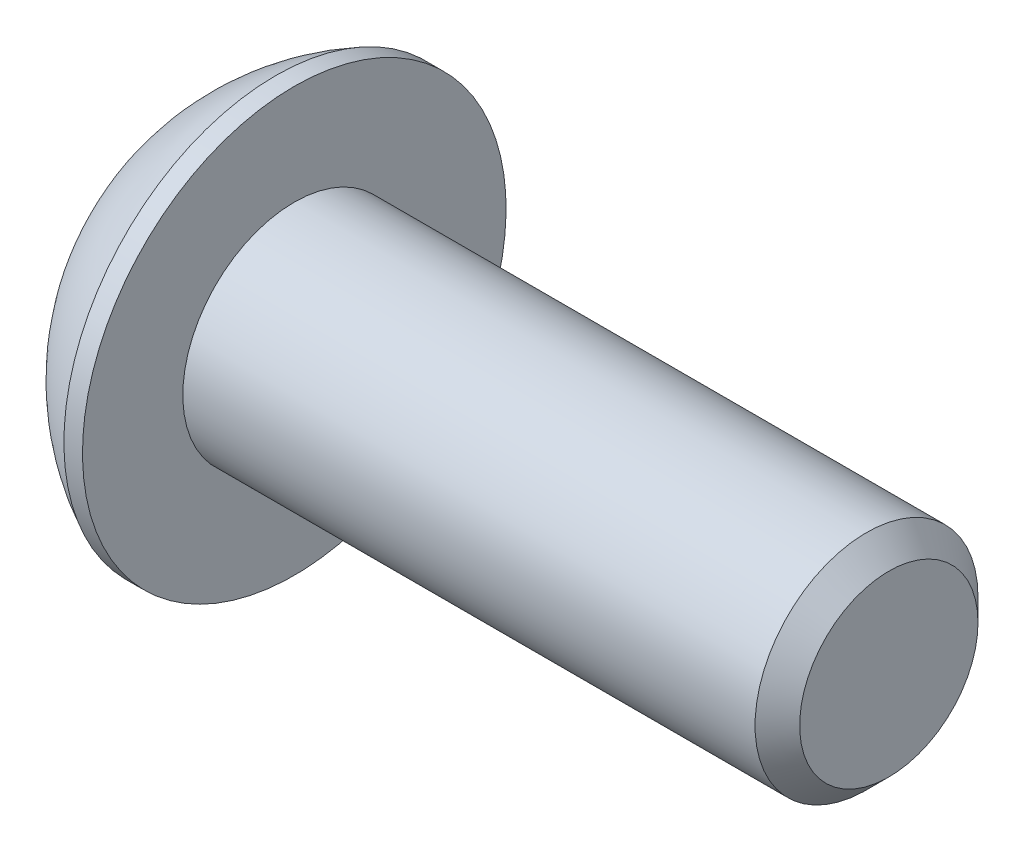
SolidWorks part; units mm, degrees
material "Plain Carbon Steel"
ref_plane "Front Plane" through (0, 0, 0) normal (0, 0, 1) x (1, 0, 0)
ref_plane "Top Plane" through (0, 0, 0) normal (0, 1, 0) x (1, 0, 0)
ref_plane "Right Plane" through (0, 0, 0) normal (1, 0, 0) x (0, 0, -1)
sketch "Sketch2" plane through (0, 0, 0) normal (1, 0, 0) x (0, 0, -1)
  circle A0 centre (0, 0) radius 1.5
  dimension "D1" = 3
extrude "Boss-Extrude1" add sketch "Sketch2" against normal blind 8
chamfer "Chamfer1" distance 0.3 angle 45 1 edges at (0, 0, -1.5)
sketch "Sketch6" plane through (0, 0, 0) normal (0, 0, 1) x (1, 0, 0)
  line L0 (-9.65, 0) -> (-9.65, 1.5)
  line L1 (-9.65, 0) -> (-8, 0)
  line L2 (-8.25, 2.85) -> (-8, 2.85)
  line L6 (-8, 2.85) -> (-8, 0)
  line L8 (-8, 0) -> (-14.6471, 0) construction
  line L10 (-8, 1.5) -> (-8, -1.5) construction
  arc A0 (-9.65, 1.5) -> (-8.25, 2.85) centre (-6.8527, 0) cw
  dimension "D3" = 0.25
  dimension "D1" = 5.7
  dimension "D2" = 1.65
  dimension "D4" = 3
revolve "Revolve1" add sketch "Sketch6" angle 360 about L8
sketch "Sketch7" plane through (-9.65, 0, 0) normal (-1, 0, 0) x (0, 0, 1)
  line L1 (0, 1.1547) -> (-1, 0.5774)
  line L2 (-1, 0.5774) -> (-1, -0.5774)
  line L3 (-1, -0.5774) -> (0, -1.1547)
  line L4 (0, -1.1547) -> (1, -0.5774)
  line L5 (1, -0.5774) -> (1, 0.5774)
  line L6 (1, 0.5774) -> (0, 1.1547)
  circle A0 centre (0, 0) radius 1 construction
  dimension "D1" = 2
extrude "Cut-Extrude1" cut sketch "Sketch7" against normal blind 1.2
sketch "Sketch8" plane through (-9.65, 0, 0) normal (-1, 0, 0) x (0, 0, 1)
  circle A0 centre (0, 0) radius 1.2047
  dimension "D1" = 0.05
extrude "Cut-Extrude2" cut sketch "Sketch8" against normal blind 1 draft 45
